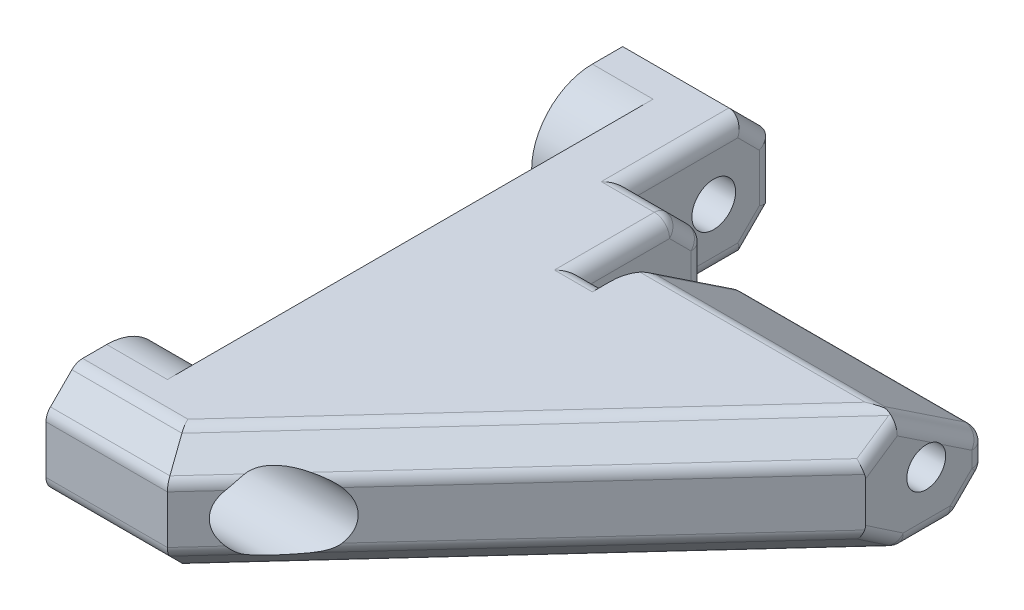
SolidWorks part; units mm, degrees
ref_plane "Front Plane" through (0, 0, 0) normal (0, 0, 1) x (1, 0, 0)
ref_plane "Top Plane" through (0, 0, 0) normal (0, 1, 0) x (1, 0, 0)
ref_plane "Right Plane" through (0, 0, 0) normal (1, 0, 0) x (0, 0, -1)
sketch "Sketch10" plane through (0, 0, 0) normal (0, 1, 0) x (1, 0, 0)
  line L0 (0, 0) -> (12.7, 0)
  line L1 (12.7, 0) -> (12.7, -12.7)
  line L2 (12.7, -12.7) -> (18.2563, -12.7)
  line L5 (47.625, -12.7) -> (47.625, -25.4)
  line L6 (47.625, -25.4) -> (12.7, -63.5)
  line L7 (12.7, -63.5) -> (0, -63.5)
  line L8 (0, -63.5) -> (0, 0)
  line L13 (18.2563, -12.7) -> (18.2563, -25.4)
  line L14 (18.2563, -25.4) -> (20.6375, -25.4)
  line L15 (20.6375, -25.4) -> (20.6375, -12.7)
  line L16 (20.6375, -12.7) -> (47.625, -12.7)
  dimension "D1" = 63.5
  dimension "D2" = 12.7
  dimension "D3" = 12.7
  dimension "D4" = 12.7
  dimension "D5" = 2.3813
  dimension "D6" = 12.7
  dimension "D7" = 26.9875
  dimension "D8" = 47.625
extrude "Boss-Extrude3" add sketch "Sketch10" along normal blind 12.7
sketch "Sketch11" plane through (47.625, 0, 0) normal (1, 0, 0) x (0, 0, -1)
  line L1 (-25.4, 0) -> (-12.7, 0) construction
  line L2 (-12.7, 12.7) -> (-12.7, 0) construction
  circle A0 centre (-19.05, 6.35) radius 2.032
  point P2 (0, 0)
  dimension "D3" = 4.064
  dimension "D1" = 6.35
  dimension "D2" = 6.35
extrude "Cut-Extrude5" cut sketch "Sketch11" against normal blind 38.1
sketch "Sketch12" plane through (0, 0, 0) normal (-1, 0, 0) x (0, 0, 1)
  line L0 (0, 12.7) -> (0, 0) construction
  line L1 (0, 0) -> (63.5, 0) construction
  circle A0 centre (6.35, 6.35) radius 2.286
  circle A1 centre (57.15, 6.35) radius 2.286
  point P9 (57.0192, 9.9926)
  dimension "D2" = 4.572
  dimension "D1" = 50.8
  dimension "D3" = 6.35
  dimension "D4" = 6.35
extrude "Cut-Extrude6" cut sketch "Sketch12" against normal up to next
sketch "Sketch13" plane through (0, 0, 0) normal (-1, 0, 0) x (0, 0, 1)
  circle A0 centre (57.15, 6.35) radius 4.064
  dimension "D1" = 8.128
extrude "Cut-Extrude7" cut sketch "Sketch13" against normal up to next from offset 6.35 offset against normal yes
chamfer "Chamfer1" distance 3.175 angle 45 9 edges at (6.35, 12.7, 0) (6.35, 0, 0) (30.1625, 0, 44.45) (6.35, 0, 63.5) (30.1625, 12.7, 44.45) (6.35, 12.7, 63.5) (15.4781, 0, 12.7) (34.1313, 0, 12.7) (15.4781, 12.7, 12.7)
chamfer "Chamfer2" distance 6.35 distance2 9.525 1 edges at (34.1313, 12.7, 12.7) first distance on face at (34.1313, 7.9375, 12.7)
fillet "Fillet1" radius 1.5875 40 edges at (14.4477, 3.175, 61.5934) (14.4477, 9.525, 61.5934) (5.6517, 12.7, 60.325) (6.35, 9.525, 63.5) (6.35, 3.175, 63.5) (5.6517, 0, 60.325) (29.4642, 0, 40.5132) (28.7658, 12.7, 41.275) (34.2356, 3.175, 40.0066) (34.2356, 9.525, 40.0066) (47.625, 10.8568, 23.429) (47.625, 1.5875, 23.0507) (47.625, 0, 18.2882) (47.625, 1.5875, 14.2875) (47.625, 4.7625, 12.7) (47.625, 9.2693, 17.079) (20.6375, 9.525, 17.4625) (20.6375, 4.7625, 12.7) (20.6375, 1.5875, 14.2875) (20.6375, 0, 20.6375) (18.2563, 0, 20.6375) (18.2563, 1.5875, 14.2875) (18.2563, 12.7, 20.6375) (18.2563, 11.1125, 14.2875) (18.2563, 6.35, 12.7) (19.4469, 0, 25.4) (19.4469, 12.7, 25.4) (34.1313, 3.175, 12.7) (34.1313, 0, 15.875) (15.4781, 0, 15.875) (15.4781, 3.175, 12.7) (34.1313, 6.35, 12.7) (33.4329, 12.7, 22.225) (15.4781, 12.7, 15.875) (15.4781, 9.525, 12.7) (12.7, 12.7, 9.525) (12.7, 0, 9.525) (12.7, 1.5875, 1.5875) (12.7, 6.35, 0) (12.7, 11.1125, 1.5875)
sketch "Sketch14" plane through (0, 0, 0) normal (-1, 0, 0) x (0, 0, 1)
  line L0 (3.175, 0) -> (59.6674, 0) construction
  line L1 (3.175, 12.7) -> (59.6674, 12.7) construction
  line L2 (6.35, 0) -> (57.15, 0)
  line L3 (6.35, 12.7) -> (57.15, 12.7)
  arc A0 (57.15, 12.7) -> (57.15, 0) centre (57.15, 6.35) ccw
  arc A1 (6.35, 0) -> (6.35, 12.7) centre (6.35, 6.35) ccw
extrude "Cut-Extrude10" cut sketch "Sketch14" against normal blind 6.35
sketch "Sketch15" plane through (6.35, 0, 0) normal (-1, 0, 0) x (0, 0, 1)
  line L0 (0, 9.525) -> (0, 3.175) construction
  circle A0 centre (31.75, 6.35) radius 4.445
  point P5 (0, 6.35)
  dimension "D1" = 8.89
  dimension "D2" = 31.75
extrude "Cut-Extrude11" cut sketch "Sketch15" against normal blind 3.175
